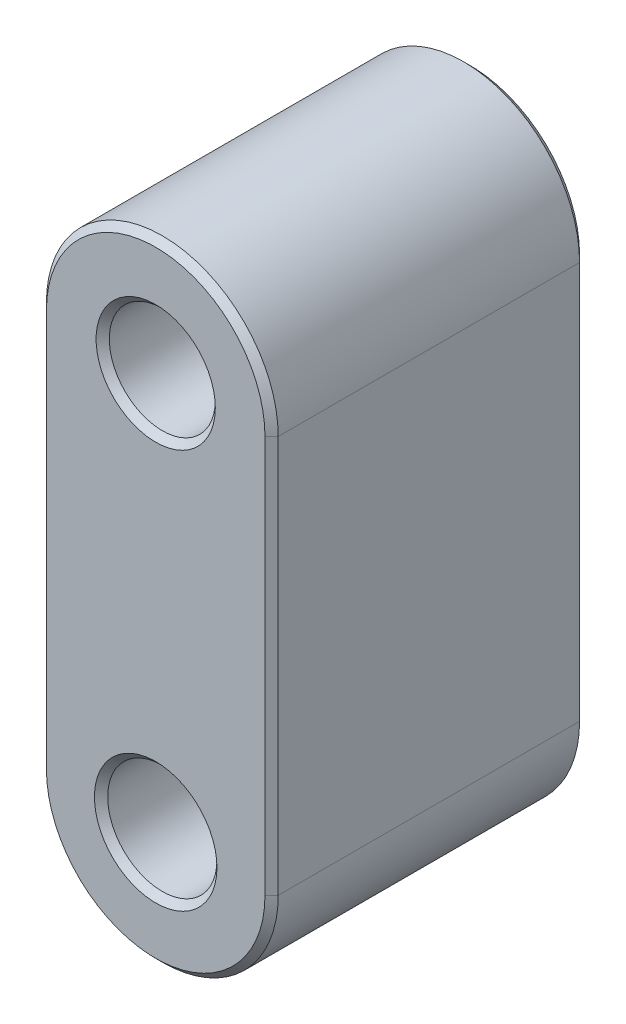
SolidWorks part; units mm, degrees
ref_plane "Front" through (0, 0, 0) normal (0, 0, 1) x (1, 0, 0)
ref_plane "Top" through (0, 0, 0) normal (0, 1, 0) x (1, 0, 0)
ref_plane "Right" through (0, 0, 0) normal (1, 0, 0) x (0, 0, -1)
sketch "Sketch1" plane through (0, 0, 0) normal (0, 0, 1) x (1, 0, 0)
  line L3 (-3.5, 0) -> (-1.6, 0) construction
  line L23 (1.65, -12) -> (3.55, -12) construction
  line L33 (-3.5, 0) -> (-3.5, -12)
  line L34 (3.5, -12) -> (3.5, 0)
  circle A0 centre (0, 0) radius 3.5 construction
  circle A3 centre (0, 0) radius 1.6
  circle A12 centre (0, -12) radius 1.65
  circle A13 centre (0, -12) radius 4.25 construction
  arc A22 (-3.5, 0) -> (3.5, 0) centre (0, 0) cw
  arc A28 (-3.5, -12) -> (3.5, -12) centre (0, -12) ccw
  dimension "D1" = 3.2
  dimension "D3" = 8.5
  dimension "D6" = 3.3
  dimension "D7" = 3.5
  dimension "D2" = 1.9
  dimension "D5" = 12
extrude "Boss-Extrude1" add sketch "Sketch1" along normal mid plane 9.5 contours A3 region at (0, -5.9711, 0)
sketch "Sketch2" plane through (0, 0, 0) normal (0, 0, 1) x (1, 0, 0)
  line L0 (-3.4942, -12.2017) -> (-4.2702, 1.2426)
  line L1 (0, 0) -> (0, 8.0844) construction
  line L2 (0, 0) -> (-0.6762, 1.4501) construction
  line L3 (-0.6762, 1.4501) -> (-2.1131, 4.5315) construction
  line L4 (-2.1131, 4.5315) -> (-2.1976, 4.7128) construction
  line L5 (2.9205, 1.6033) -> (3.5, -12)
  line L6 (3.5, -12) -> (3.5, 0) construction
  arc A0 (-4.2702, 1.2426) -> (2.9205, 1.6033) centre (-0.6762, 1.4501) cw
  circle A1 centre (0, 0) radius 5 construction
  arc A2 (-3.5, -12) -> (3.5, -12) centre (0, -12) ccw construction
  dimension "D2" = 10
  dimension "D4" = 3.6
  dimension "D1" = 0.2
  dimension "D3" = 25
extrude "Spring" [suppressed] add sketch "Sketch2" along normal through all and the other way through all thin thin type one direction wall 1
fillet "Spring Inside Fillets" [suppressed] radius 0.25
chamfer "Deburs" [suppressed] distance 0.2 angle 45
sketch "Sketch3" [suppressed] plane through (-4.1845, -0.2415, 0) normal (-0.9983, -0.0576, 0) x (0, 0, 1)
  line L1 (0, -1.0134) -> (0, -9.4801) construction
  line L6 (4.55, 1.4866) -> (-4.55, 1.4866) construction
  line L8 (4.55, -11.9801) -> (-4.55, -11.9801) construction
  dimension "D1" = 2.5
  dimension "D2" = 2.5
sketch "Sketch4" [suppressed] plane through (-4.1845, -0.2415, 0) normal (-0.9983, -0.0576, 0) x (0, 0, 1)
  line L0 (0, -1.0134) -> (0, -9.4801)
  line L1 (-2, -3.0134) -> (0, -1.0134)
  line L2 (0, -1.0134) -> (2, -3.0134)
  line L3 (0, -1.0134) -> (0, -9.4801) construction
  line L6 (0, -11.9191) -> (0, 0.0453) construction
  dimension "D1" = 45
  dimension "D2" = 2
extrude "Arrow Point" [suppressed] add sketch "Sketch4" along normal blind 0.2 draft 55 thin contours L1 | L2 thin type one direction wall 0.8
sketch "Sketch5" [suppressed] plane through (-4.1845, -0.2415, 0) normal (-0.9983, -0.0576, 0) x (0, 0, 1)
  line L0 (0, -1.4173) -> (0, -9.4801)
  line L1 (0, -1.0134) -> (0, -9.4801) construction
extrude "Arrow Shaft" [suppressed] add sketch "Sketch5" along normal blind 0.2 draft 55 thin thin type mid plane wall 0.8
chamfer "Deburs no Spring" distance 0.2 angle 45 12 edges at (0, -15.5, -4.75) (3.5, -6, -4.75) (0, 3.5, -4.75) (-3.5, -6, -4.75) (1.65, -12, -4.75) (1.6, 0, -4.75) (0, 3.5, 4.75) (3.5, -6, 4.75) (0, -15.5, 4.75) (-3.5, -6, 4.75) (1.65, -12, 4.75) (1.6, 0, 4.75)
equation "\"D1@Sketch1\"=\"Clearance Hole Diameter@Box Assy.Assembly\"+.05mm"
equation "\"D6@Sketch1\"=\"Clearance Hole Diameter@Box Assy.Assembly\"+.15mm"
